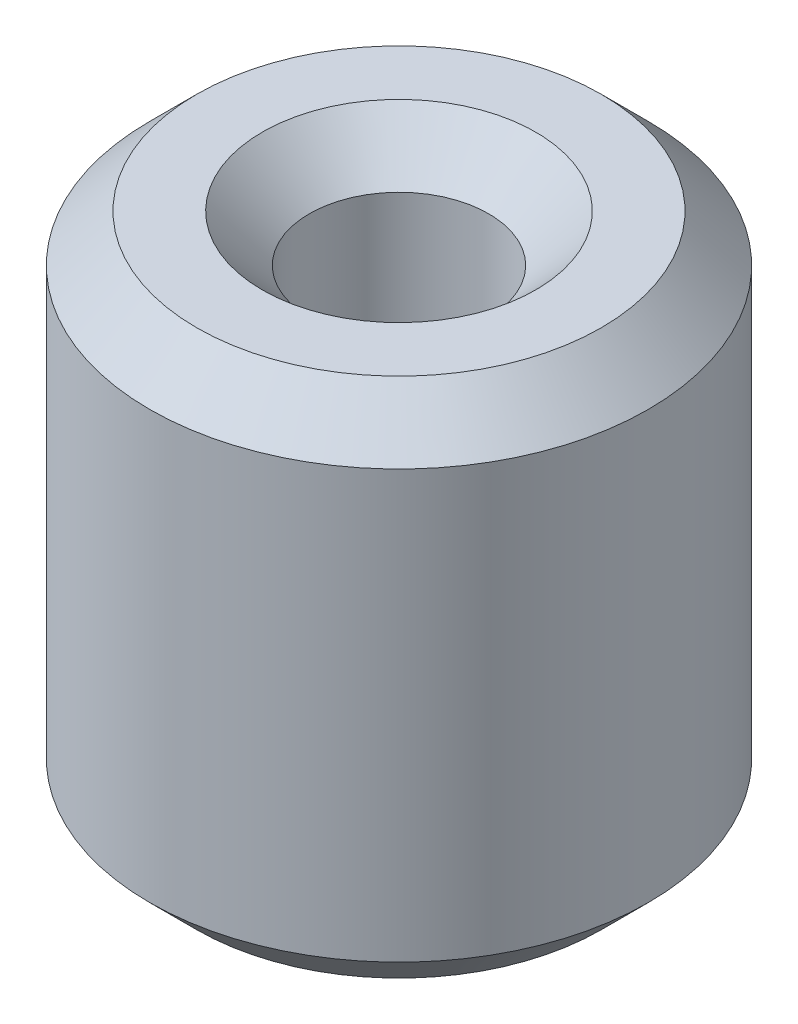
SolidWorks part; units mm, degrees
ref_plane "Front Plane" through (0, 0, 0) normal (0, 0, 1) x (1, 0, 0)
ref_plane "Top Plane" through (0, 0, 0) normal (0, 1, 0) x (1, 0, 0)
ref_plane "Right Plane" through (0, 0, 0) normal (1, 0, 0) x (0, 0, -1)
sketch "Sketch1" plane through (0, 0, 0) normal (0, 1, 0) x (1, 0, 0)
  circle A0 centre (0, 0) radius 10
  dimension "SLEEVE_OD" = 20
extrude "Boss-Extrude1" add sketch "Sketch1" along normal blind 20.9052
sketch "Sketch2" plane through (0, 0, 0) normal (0, 1, 0) x (1, 0, 0)
  circle A0 centre (0, 0) radius 3.5936
  dimension "BORE_D" = 7.1873
extrude "Cut-Extrude1" cut sketch "Sketch2" along normal through all
chamfer "Chamfer1" distance 1.889 angle 45 4 edges at (0, 20.9052, 3.5936) (0, 0, 3.5936) (0, 0, 10) (0, 20.9052, 10)
